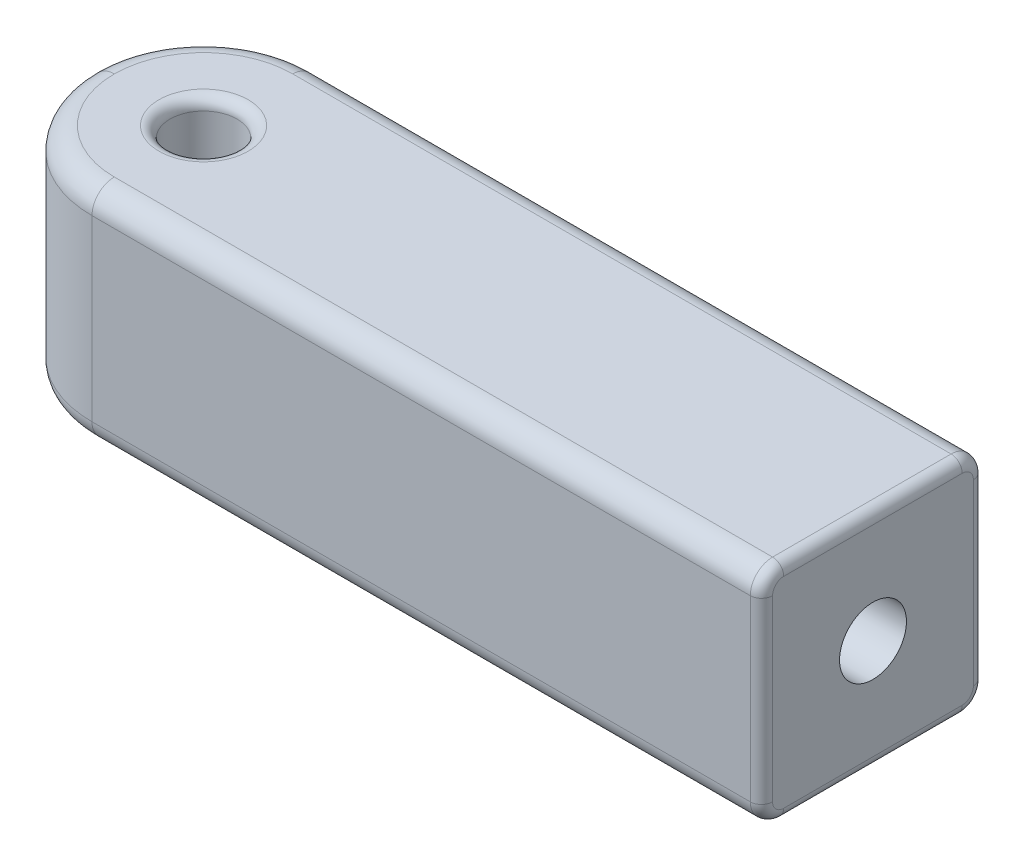
SolidWorks part; units mm, degrees
ref_plane "Alzado" through (0, 0, 0) normal (0, 0, 1) x (1, 0, 0)
ref_plane "Planta" through (0, 0, 0) normal (0, 1, 0) x (1, 0, 0)
ref_plane "Vista lateral" through (0, 0, 0) normal (1, 0, 0) x (0, 0, -1)
sketch "Croquis1" plane through (0, 0, 0) normal (0, 0, 1) x (1, 0, 0)
  line L1 (0, 0) -> (175, 0)
  line L2 (0, 0) -> (0, 50)
  line L3 (0, 50) -> (175, 50)
  line L4 (175, 0) -> (175, 50)
extrude "Saliente-Extruir1" add sketch "Croquis1" along normal blind 50
fillet "Redondeo1" radius 25 2 edges at (0, 25, 0) (0, 25, 50)
sketch "Croquis2" plane through (175, 0, 0) normal (1, 0, 0) x (0, 0, -1)
  circle A0 centre (-25, 25) radius 7.5
extrude "Cortar-Extruir1" cut sketch "Croquis2" against normal blind 15
sketch "Croquis3" plane through (0, 50, 0) normal (0, 1, 0) x (1, 0, 0)
  circle A0 centre (25, -25) radius 7.5
extrude "Cortar-Extruir2" cut sketch "Croquis3" against normal through all
fillet "Redondeo2" radius 5 8 edges at (7.3223, 0, 7.3223) (7.3223, 0, 42.6777) (7.3223, 50, 7.3223) (7.3223, 50, 42.6777) (100, 0, 0) (100, 0, 50) (100, 50, 0) (100, 50, 50)
fillet "Redondeo3" radius 2.5 2 edges at (25, 0, 32.5) (25, 50, 32.5)
fillet "Redondeo4" radius 2.5 8 edges at (175, 1.4645, 48.5355) (175, 48.5355, 48.5355) (175, 48.5355, 1.4645) (175, 1.4645, 1.4645) (175, 0, 25) (175, 25, 0) (175, 50, 25) (175, 25, 50)
